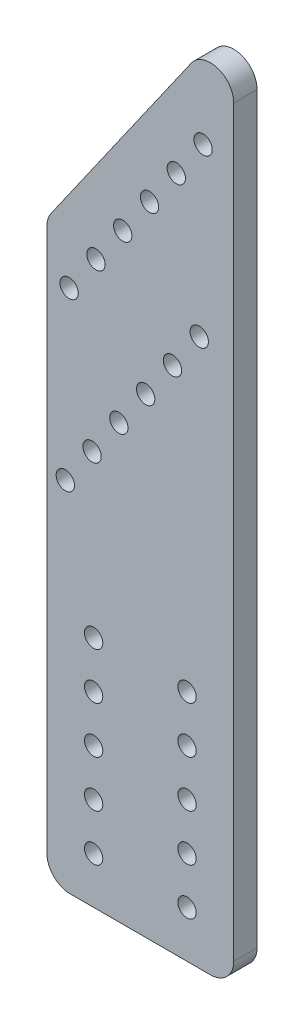
SolidWorks part; units mm, degrees
material "6061-T6 (SS)"
ref_plane "Front Plane" through (0, 0, 0) normal (0, 0, 1) x (1, 0, 0)
ref_plane "Top Plane" through (0, 0, 0) normal (0, 1, 0) x (1, 0, 0)
ref_plane "Right Plane" through (0, 0, 0) normal (1, 0, 0) x (0, 0, -1)
sketch "Sketch1" plane through (0, 0, 0) normal (0, 0, 1) x (1, 0, 0)
  line L0 (0, 156.0501) -> (50.8, 228.6)
  line L1 (0, 0) -> (50.8, 0)
  line L2 (0, 0) -> (0, 156.0501)
  line L3 (0, 228.6) -> (50.8, 228.6) construction
  line L4 (50.8, 0) -> (50.8, 228.6)
  line L5 (0, 156.0501) -> (0, 228.6) construction
  dimension "D1" = 50.8
  dimension "D2" = 55
  dimension "D3" = 228.6
extrude "Boss-Extrude1" add sketch "Sketch1" along normal blind 6.35
sketch "Sketch2" plane through (0, 0, 0) normal (0, 0, -1) x (-1, 0, 0)
  line L2 (-50.8, 12.7) -> (0, 12.7) construction
  line L3 (-50.8, 0) -> (-50.8, 228.6) construction
  line L4 (0, 156.0501) -> (0, 0) construction
  line L5 (0, 0) -> (-50.8, 0) construction
  line L6 (-50.8, 228.6) -> (-92.4129, 199.4623) construction
  line L7 (-50.8, 228.6) -> (0, 156.0501) construction
  line L8 (-92.4129, 199.4623) -> (-41.6129, 126.9124) construction
  line L9 (0, 156.0501) -> (-41.6129, 126.9124) construction
  line L10 (-50.8, 228.6) -> (0, 156.0501) construction
  line L11 (-88.2447, 193.5095) -> (-46.6318, 222.6472) construction
  circle A33 centre (-38.1, 12.7) radius 2.4892
  circle A34 centre (-12.7, 12.7) radius 2.4892
  circle A35 centre (-12.7, 25.4) radius 2.4892
  circle A36 centre (-38.1, 25.4) radius 2.4892
  circle A37 centre (-12.7, 38.1) radius 2.4892
  circle A38 centre (-38.1, 38.1) radius 2.4892
  circle A39 centre (-12.7, 50.8) radius 2.4892
  circle A40 centre (-38.1, 50.8) radius 2.4892
  circle A41 centre (-12.7, 63.5) radius 2.4892
  circle A42 centre (-38.1, 63.5) radius 2.4892
  circle A43 centre (-77.8415, 200.7939) radius 2.4892 construction
  circle A44 centre (-57.035, 215.3628) radius 2.4892 construction
  circle A45 centre (-49.7506, 204.9596) radius 2.4892 construction
  circle A46 centre (-70.5571, 190.3907) radius 2.4892 construction
  circle A47 centre (-42.4662, 194.5563) radius 2.4892
  circle A48 centre (-63.2727, 179.9875) radius 2.4892 construction
  circle A49 centre (-35.1818, 184.1531) radius 2.4892
  circle A50 centre (-55.9882, 169.5843) radius 2.4892 construction
  circle A51 centre (-27.8974, 173.7499) radius 2.4892
  circle A52 centre (-48.7038, 159.181) radius 2.4892 construction
  circle A53 centre (-20.6129, 163.3466) radius 2.4892
  circle A54 centre (-41.4194, 148.7778) radius 2.4892
  circle A55 centre (-13.3285, 152.9434) radius 2.4892
  circle A56 centre (-34.135, 138.3746) radius 2.4892
  circle A57 centre (-6.0441, 142.5402) radius 2.4892
  circle A58 centre (-26.8506, 127.9713) radius 2.4892
  circle A59 centre (1.2403, 132.1369) radius 2.4892 construction
  circle A60 centre (-19.5661, 117.5681) radius 2.4892
  circle A61 centre (8.5247, 121.7337) radius 2.4892 construction
  circle A62 centre (-12.2817, 107.1649) radius 2.4892
  circle A63 centre (15.8092, 111.3305) radius 2.4892 construction
  circle A64 centre (-4.9973, 96.7616) radius 2.4892
  circle A65 centre (23.0936, 100.9272) radius 2.4892 construction
  circle A66 centre (2.2871, 86.3584) radius 2.4892 construction
  dimension "D1" = 12.7
  dimension "D2" = 25.4
  dimension "D3" = 4.9784
  dimension "D4" = 12.7
  dimension "D5" = 12.7
  dimension "D6" = 50.8
  dimension "D8" = 12.7
  dimension "D9" = 25.4
  dimension "D10" = 7.267
  dimension "D11" = 12.7
  dimension "D7" = 5
  dimension "D12" = 12
extrude "Cut-Extrude1" cut sketch "Sketch2" against normal through all
fillet "Fillet1" radius 6.35 4 edges at (0, 156.0501, 3.175) (50.8, 0, 3.175) (0, 0, 3.175) (50.8, 228.6, 3.175)
